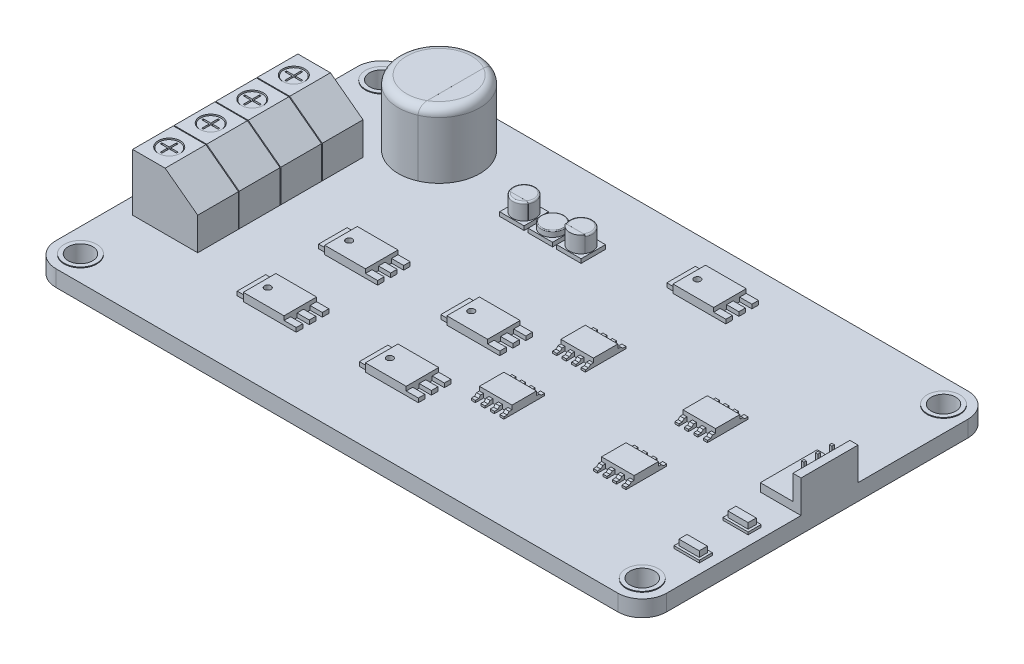
SolidWorks part; units mm, degrees
ref_plane "Front Plane" through (0, 0, 0) normal (0, 0, 1) x (1, 0, 0)
ref_plane "Top Plane" through (0, 0, 0) normal (0, 1, 0) x (1, 0, 0)
ref_plane "Right Plane" through (0, 0, 0) normal (1, 0, 0) x (0, 0, -1)
sketch "Sketch1" plane through (0, 0, 0) normal (0, 1, 0) x (1, 0, 0)
  line L1 (34.5, -21.5) -> (-34.5, -21.5)
  line L2 (37.5, -18.5) -> (37.5, 18.5)
  line L3 (34.5, 21.5) -> (-34.5, 21.5)
  line L4 (-37.5, -18.5) -> (-37.5, 18.5)
  line L5 (37.5, -21.5) -> (-37.5, 21.5) construction
  line L6 (37.5, 21.5) -> (-37.5, -21.5) construction
  circle A0 centre (-34.5, 18.5) radius 1.5
  circle A1 centre (34.5, 18.5) radius 1.5
  circle A2 centre (34.5, -18.5) radius 1.5
  circle A3 centre (-34.5, -18.5) radius 1.5
  arc A4 (-34.5, -21.5) -> (-37.5, -18.5) centre (-34.5, -18.5) cw
  arc A5 (34.5, -21.5) -> (37.5, -18.5) centre (34.5, -18.5) ccw
  arc A6 (-34.5, 21.5) -> (-37.5, 18.5) centre (-34.5, 18.5) ccw
  arc A7 (37.5, 18.5) -> (34.5, 21.5) centre (34.5, 18.5) ccw
  point P0 (0, 0)
  dimension "D3" = 3
  dimension "D8" = 3
  dimension "D1" = 75
  dimension "D2" = 43
  dimension "D4" = 37
  dimension "D5" = 18.5
  dimension "D6" = 69
  dimension "D7" = 34.5
extrude "Boss-Extrude1" add sketch "Sketch1" along normal blind 2
ref_plane "Plane1" through (0, 0, 1) normal (0, 0, 1) x (1, 0, 0)
sketch "Sketch8" plane through (0, 0, 1) normal (0, 0, 1) x (1, 0, 0)
  line L0 (-35.5, 2) -> (-35.5, 9)
  line L1 (-34.5, 2) -> (34.5, 2) construction
  line L2 (-35.5, 9) -> (-31.5, 9)
  line L3 (-31.5, 9) -> (-27.5, 6)
  line L4 (-27.5, 6) -> (-27.5, 2)
  line L5 (-27.5, 2) -> (-35.5, 2)
  line L6 (-37.5, 2) -> (-37.5, 0) construction
  dimension "D1" = 2
  dimension "D2" = 7
  dimension "D3" = 8
  dimension "D4" = 4
  dimension "D5" = 4
extrude "Boss-Extrude3" add sketch "Sketch8" along normal blind 5
sketch "Sketch9" plane through (0, 9, 0) normal (0, 1, 0) x (1, 0, 0)
  line L0 (-31.5, -1) -> (-35.5, -1) construction
  line L1 (-35.5, -6) -> (-35.5, -1) construction
  line L2 (-33.5, -3.5) -> (-33.5, -2.5)
  line L3 (-33.4, -4.5) -> (-33.4, -3.5)
  line L4 (-33.5, -4.5) -> (-33.5, -3.5)
  line L5 (-32.5, -3.5) -> (-34.5, -3.5)
  line L6 (-33.4, -3.5) -> (-33.4, -2.5)
  line L7 (-32.5, -3.4) -> (-34.5, -3.4)
  line L8 (-33.6, -4.5) -> (-33.6, -3.5)
  line L9 (-33.6, -3.5) -> (-33.6, -2.5)
  line L10 (-32.5, -3.6) -> (-34.5, -3.6)
  line L11 (-33.6, -2.5) -> (-33.4, -2.5)
  line L12 (-32.5, -3.4) -> (-32.5, -3.6)
  line L13 (-33.4, -4.5) -> (-33.6, -4.5)
  line L14 (-34.5, -3.6) -> (-34.5, -3.4)
  circle A0 centre (-33.5, -3.5) radius 1.25
  circle A1 centre (-33.5, -3.5) radius 1.35
  dimension "D1" = 2.5
  dimension "D2" = 2.5
  dimension "D3" = 2
  dimension "D5" = 1
  dimension "D6" = 1
  dimension "D7" = 1
  dimension "D8" = 1
  dimension "D4" = 0.1
  dimension "D9" = 0.1
  dimension "D10" = 0.1
extrude "Cut-Extrude2" cut sketch "Sketch9" against normal blind 2.5 contours A1 A0 region at (-34.8118, 9, 3.5)
extrude "Cut-Extrude4" cut sketch "Sketch9<4>" against normal blind 0.1 contours A0
sketch "Sketch9<4>" plane through (0, 9, 0) normal (0, 1, 0) x (1, 0, 0) same geometry as "Sketch9"
extrude "Cut-Extrude3" cut sketch "Sketch9<3>" against normal blind 0.5 contours L11 L2 L7 L6 | L11 L9 L7 L2 | L13 L3 L10 L4 | L13 L4 L10 L8 | L7 L14 L10 L12 region at (-33.55, 9, 2.95) region at (-33.45, 9, 2.95) region at (-33.45, 9, 4.05) region at (-33.55, 9, 4.05)
sketch "Sketch9<3>" plane through (0, 9, 0) normal (0, 1, 0) x (1, 0, 0) same geometry as "Sketch9"
pattern_linear "LPattern1" count 2 spacing 5.1 along (0, 0, 1) count 3 spacing 5.1 along (0, 0, -1) of "Boss-Extrude3", "Cut-Extrude2", "Cut-Extrude4", "Cut-Extrude3" pattern seed only yes
sketch "Sketch10" plane through (0, 2, 0) normal (0, 1, 0) x (1, 0, 0)
  circle A0 centre (-34.5, 18.5) radius 1.5 construction
  circle A11 centre (-34.5, 18.5) radius 2
  circle A12 centre (-34.5, 18.5) radius 2
  circle A14 centre (34.5, 18.5) radius 2
  circle A15 centre (34.5, 18.5) radius 2
  circle A17 centre (34.5, -18.5) radius 2
  circle A18 centre (34.5, -18.5) radius 2
  circle A19 centre (-34.5, -18.5) radius 1.5
  circle A20 centre (-34.5, -18.5) radius 2
  circle A21 centre (-34.5, -18.5) radius 2
  circle A22 centre (-34.5, 18.5) radius 1.5
  circle A23 centre (34.5, 18.5) radius 1.5
  circle A24 centre (34.5, -18.5) radius 1.5
  dimension "D1" = 0.5
  dimension "D2" = 0.5
  dimension "D3" = 0.5
  dimension "D4" = 0.5
extrude "Boss-Extrude4" add sketch "Sketch10" along normal blind 0.1
sketch "Sketch11" plane through (0, 2, 0) normal (0, 1, 0) x (1, 0, 0)
  circle A0 centre (-23.5927, 14.6414) radius 5
  point P2 (0, 0)
  point P3 (-17.5, 14.1677)
  point P4 (0, 0)
  point P6 (-23.5927, 14.6414)
  point P8 (0, 0)
  point P9 (0, 0)
  dimension "D2" = 10
extrude "Boss-Extrude5" add sketch "Sketch11" along normal blind 8
fillet "Fillet1" radius 1 1 edges at (-23.5927, 10, -9.6414)
sketch "Sketch12" plane through (0, 2, 0) normal (0, 1, 0) x (1, 0, 0)
  line L0 (-37.5, 18.5) -> (-37.5, -18.5) construction
  line L1 (-19.5, -3.5) -> (-14.5, -3.5)
  line L2 (-19.5, -3.5) -> (-19.5, 0.5)
  line L3 (-19.5, 0.5) -> (-14.5, 0.5)
  line L4 (-14.5, -3.5) -> (-14.5, 0.5)
  line L5 (-34.5, -21.5) -> (34.5, -21.5) construction
  line L6 (-14.5, -3.5) -> (-13, -3.5)
  line L7 (-13, -3.5) -> (-13, -2.7)
  line L8 (-13, -2.7) -> (-14.5, -2.7)
  line L9 (-14.5, -1.901) -> (-13, -1.901)
  line L10 (-13, -1.901) -> (-13, -1.101)
  line L11 (-13, -1.101) -> (-14.5, -1.101)
  line L12 (-14.5, 0.5) -> (-13, 0.5)
  line L13 (-13, 0.5) -> (-13, -0.301)
  line L14 (-13, -0.301) -> (-14.5, -0.301)
  circle A0 centre (-18.5, -1.5) radius 0.4
  point P21 (-19.5, -1.5)
  dimension "D10" = 0.8
  dimension "D1" = 4
  dimension "D2" = 5
  dimension "D3" = 18
  dimension "D4" = 18
  dimension "D5" = 0.8
  dimension "D6" = 0.8
  dimension "D7" = 0.801
  dimension "D8" = 0.8
  dimension "D9" = 1.5
  dimension "D11" = 1
extrude "Boss-Extrude6" add sketch "Sketch12" along normal blind 1 contours L1 L4 L3 L2 region at (-16.9613, 2, 1.5)
extrude "Boss-Extrude7" add sketch "Sketch12<3>" along normal blind 0.5 contours L14 L13 L12 L4 | L10 L11 L4 L9 | L7 L8 L4 L6 region at (-13.75, 2, 3.1) region at (-13.75, 2, -0.0995) region at (-13.75, 2, 1.501)
sketch "Sketch12<3>" plane through (0, 2, 0) normal (0, 1, 0) x (1, 0, 0) same geometry as "Sketch12"
sketch "Sketch13" plane through (-19.5, 0, 0) normal (-1, 0, 0) x (0, 0, 1)
  line L0 (3.5, 2) -> (-0.5, 2) construction
  line L1 (-0.25, 2) -> (3.25, 2)
  line L2 (-0.25, 2) -> (-0.25, 2.5025)
  line L3 (-0.25, 2.5025) -> (3.25, 2.5025)
  line L4 (3.25, 2) -> (3.25, 2.5025)
  line L5 (3.5, 3) -> (-0.5, 3) construction
  point P6 (1.5, 2.5025)
  point P9 (1.5, 3)
  dimension "D1" = 0.5025
  dimension "D2" = 3.5
extrude "Boss-Extrude8" add sketch "Sketch13" along normal blind 1
pattern_linear "LPattern3" count 2 spacing 10 along (0, 0, 1) count 2 spacing 15 along (1, 0, 0) of "Boss-Extrude6", "Boss-Extrude7", "Boss-Extrude8"
sketch "Sketch14" plane through (0, 10, 0) normal (0, 1, 0) x (1, 0, 0)
  line L0 (-21.5927, 19.2239) -> (-21.5927, 10.0588)
  circle A0 centre (-23.5927, 14.6414) radius 5
  circle M4 centre (-23.5927, 14.6414) radius 4
  dimension "D1" = 10
  dimension "D2" = 3
extrude "Cut-Extrude5" cut sketch "Sketch14" against normal up to surface (8 mm away) contours L0 M4 | L0 A0 M4 region at (-19.4901, 10, -17.3272) region at (-20.7726, 10, -14.6414) up to face at (-15.9375, 2, 11.5004)
sketch "Sketch15" plane through (0, 2, 0) normal (0, 1, 0) x (1, 0, 0)
  line L0 (-21.5917, 19.2235) -> (-21.5917, 10.0588)
  line L3 (-21.5927, 19.2239) -> (-21.5927, 10.0588) construction
  circle A0 centre (-23.5927, 14.6414) radius 5
  point P3 (-21.5917, 19.2235)
  point P4 (-21.5927, 10.0588)
  dimension "D1" = 10
  dimension "D3" = 0.001
extrude "Boss-Extrude9" add sketch "Sketch15" along normal up to surface (8 mm away) contours L0 A0 region at (-20.3547, 2, -14.6414) up to face at (-24.5927, 10, -14.6414)
fillet "Fillet2" radius 1 1 edges at (-18.5927, 10, -14.6414)
sketch "Sketch16" plane through (0, 2, 0) normal (0, 1, 0) x (1, 0, 0)
  line L0 (6, 13.767) -> (11, 13.767)
  line L1 (6, 13.767) -> (6, 17.767)
  line L2 (6, 17.767) -> (11, 17.767)
  line L3 (11, 13.767) -> (11, 17.767)
  line L4 (11, 17.767) -> (12.5, 17.767)
  line L5 (12.5, 17.767) -> (12.5, 16.967)
  line L6 (12.5, 16.967) -> (11, 16.967)
  line L7 (11, 16.167) -> (12.5, 16.167)
  line L8 (12.5, 16.167) -> (12.5, 15.367)
  line L9 (12.5, 15.367) -> (11, 15.367)
  line L10 (11, 13.767) -> (12.5, 13.767)
  line L11 (12.5, 13.767) -> (12.5, 14.567)
  line L12 (12.5, 14.567) -> (11, 14.567)
  circle A0 centre (7, 15.767) radius 0.4
  point P5 (6, 15.767)
  point P18 (0, 0)
  point P19 (0, 0)
  point P20 (7, 15.767)
  dimension "D9" = 0.8
  dimension "D1" = 4
  dimension "D2" = 5
  dimension "D3" = 0.8
  dimension "D4" = 1.5
  dimension "D5" = 0.8
  dimension "D6" = 0.8
  dimension "D7" = 0.8
  dimension "D8" = 6
  dimension "D10" = 1
extrude "Boss-Extrude10" add sketch "Sketch16" along normal blind 1 contours L0 L3 L2 L1 region at (8.5387, 2, -15.767)
extrude "Boss-Extrude11" add sketch "Sketch16<3>" along normal blind 0.5 contours L6 L5 L4 L3 | L9 L8 L7 L3 | L11 L12 L3 L10 region at (11.75, 2, -14.167) region at (11.75, 2, -17.367) region at (11.75, 2, -15.767)
sketch "Sketch16<3>" plane through (0, 2, 0) normal (0, 1, 0) x (1, 0, 0) same geometry as "Sketch16"
sketch "Sketch17" plane through (6, 0, 0) normal (-1, 0, 0) x (0, 0, 1)
  line L0 (-13.767, 2) -> (-17.767, 2) construction
  line L1 (-17.517, 2) -> (-14.017, 2)
  line L2 (-17.517, 2) -> (-17.517, 2.5)
  line L3 (-17.517, 2.5) -> (-14.017, 2.5)
  line L4 (-14.017, 2) -> (-14.017, 2.5)
  line L5 (-13.767, 3) -> (-17.767, 3) construction
  point P6 (-15.767, 2.5)
  point P9 (-15.767, 3)
  dimension "D1" = 0.5
  dimension "D2" = 3.5
extrude "Boss-Extrude12" add sketch "Sketch17" along normal blind 1
sketch "Sketch18" plane through (0, 2, 0) normal (0, 1, 0) x (1, 0, 0)
  line L0 (5, 4) -> (5, 5)
  line L1 (5, 4) -> (9, 4)
  line L2 (5, 4) -> (5, 1)
  line L3 (5, 1) -> (9, 1)
  line L4 (9, 4) -> (9, 1)
  line L5 (5, 5) -> (5.5, 5)
  line L6 (5.5, 5) -> (5.5, 4)
  line L7 (6.1633, 4) -> (6.1633, 5)
  line L8 (6.1633, 5) -> (6.6633, 5)
  line L9 (6.6633, 5) -> (6.6633, 4)
  line L10 (7.3333, 4) -> (7.3333, 5)
  line L11 (7.3333, 5) -> (7.8333, 5)
  line L12 (7.8333, 5) -> (7.8333, 4)
  line L13 (8.5, 4) -> (8.5, 5)
  line L14 (8.5, 5) -> (9, 5)
  line L15 (9, 5) -> (9, 4)
  line L16 (9, 1) -> (9, 0)
  line L17 (9, 0) -> (8.5, 0)
  line L18 (8.5, 0) -> (8.5, 1)
  line L19 (7.8333, 1) -> (7.8333, 0)
  line L20 (7.8333, 0) -> (7.3333, 0)
  line L21 (7.3333, 0) -> (7.3333, 1)
  line L22 (6.6633, 1) -> (6.6633, 0)
  line L23 (6.6633, 0) -> (6.1633, 0)
  line L24 (6.1633, 0) -> (6.1633, 1)
  line L25 (5, 1) -> (5, 0)
  line L26 (5, 0) -> (5.5, 0)
  line L27 (5.5, 0) -> (5.5, 1)
  dimension "D1" = 3
  dimension "D2" = 4
  dimension "D3" = 0.5
  dimension "D4" = 0.5
  dimension "D5" = 0.6667
  dimension "D6" = 0.67
  dimension "D7" = 0.5
  dimension "D8" = 0.5
  dimension "D9" = 1
  dimension "D10" = 5
  dimension "D11" = 4
extrude "Boss-Extrude13" add sketch "Sketch18" along normal blind 1 contours L4 L1 L2 L3 region at (7, 2, -2.5)
extrude "Boss-Extrude14" add sketch "Sketch18<3>" along normal blind 0.5 contours L18 L17 L16 L3 | L21 L20 L19 L3 | L24 L23 L22 L3 | L26 L27 L3 L25 | L15 L14 L13 L1 | L12 L11 L10 L1 | L9 L8 L7 L1 | L6 L5 L0 L1 region at (5.25, 2, -4.5) region at (5.25, 2, -0.5) region at (6.4133, 2, -4.5) region at (6.4133, 2, -0.5) region at (7.5833, 2, -4.5) region at (7.5833, 2, -0.5) region at (8.75, 2, -4.5) region at (8.75, 2, -0.5)
sketch "Sketch18<3>" plane through (0, 2, 0) normal (0, 1, 0) x (1, 0, 0) same geometry as "Sketch18"
sketch "Sketch19" plane through (9, 0, 0) normal (1, 0, 0) x (0, 0, -1)
  line L0 (-18.5, 2) -> (18.5, 2) construction
  line L1 (0, 2.5) -> (1, 2.5)
  line L2 (0, 2.5) -> (0, 2)
  line L3 (0, 2) -> (1, 2)
  line L4 (1, 2.5) -> (1, 2)
  line L5 (1, 2.5) -> (0.6524, 2.5)
  line L6 (0.6524, 2.5) -> (0.4024, 2.25)
  line L7 (0.4024, 2.25) -> (0, 2.25)
  line L8 (2.5, 3) -> (2.5, 2) construction
  line L9 (4, 3) -> (1, 3) construction
  line L10 (5, 2) -> (0, 2) construction
  line L11 (4.5976, 2.25) -> (5, 2.25)
  line L12 (4.3476, 2.5) -> (4.5976, 2.25)
  line L13 (5, 2) -> (4, 2)
  line L14 (4, 2.5) -> (4, 2)
  line L15 (5, 2.5) -> (4, 2.5)
  line L16 (5, 2.5) -> (5, 2)
  line M9 (5, 2) -> (5, 2.5)
  line M10 (5, 2.5) -> (4, 2.5)
  line M15 (0, 2.5) -> (0, 2)
  dimension "D1" = 0.25
  dimension "D2" = 0.3476
extrude "Cut-Extrude6" cut sketch "Sketch19" against normal up to surface (4 mm away) contours L7 L6 L1 M15 | L12 L11 M10 M9 region at (9, 2.3849, -0.2686) region at (9, 2.3849, -4.7314) up to face at (5, 2.5, -2.5)
pattern_linear "LPattern4" count 2 spacing 10 along (0, 0, 1) count 2 spacing 15 along (1, 0, 0) of "Boss-Extrude13", "Cut-Extrude6", "Boss-Extrude14"
sketch "Sketch20" plane through (0, 2, 0) normal (0, 1, 0) x (1, 0, 0)
  line L1 (-12.825, 14.3088) -> (-9.825, 14.3088)
  line L2 (-12.825, 14.3088) -> (-12.825, 11.3088)
  line L3 (-12.825, 11.3088) -> (-9.825, 11.3088)
  line L4 (-9.825, 14.3088) -> (-9.825, 11.3088)
  point P4 (-12.825, 11.3088)
  dimension "D1" = 3
  dimension "D2" = 3
extrude "Boss-Extrude15" add sketch "Sketch20" along normal blind 0.5
pattern_linear "LPattern5" count 3 spacing 3.5 along (1, 0, 0) of "Boss-Extrude15"
sketch "Sketch21" plane through (0, 2.5, 0) normal (0, 1, 0) x (1, 0, 0)
  line L0 (-9.825, 14.3088) -> (-12.825, 14.3088) construction
  line L1 (-12.825, 14.3088) -> (-12.825, 11.3088) construction
  circle A0 centre (-11.325, 12.8088) radius 1.4
  point P6 (-11.325, 14.3088)
  point P10 (-12.825, 12.8088)
  dimension "D1" = 2.8
extrude "Boss-Extrude16" add sketch "Sketch21" along normal blind 2
sketch "Sketch22" plane through (0, 4.5, 0) normal (0, 1, 0) x (1, 0, 0)
  line L0 (-12.5375, 12.1088) -> (-10.1126, 12.1088)
  circle A0 centre (-11.325, 12.8088) radius 1.4
  circle M3 centre (-11.325, 12.8088) radius 1.4
  dimension "D1" = 2.8
  dimension "D2" = 0.7
extrude "Cut-Extrude7" cut sketch "Sketch22" against normal up to surface (2 mm away) contours L0 M3 region at (-11.325, 4.5, -11.8217) up to face at (-11.325, 2.5, -11.4088)
sketch "Sketch23" plane through (0, 4.5, 0) normal (0, 1, 0) x (1, 0, 0)
  line L0 (-12.5369, 12.1078) -> (-10.1132, 12.1078)
  line L1 (-12.5375, 12.1088) -> (-10.1126, 12.1088) construction
  circle A0 centre (-11.325, 12.8088) radius 1.4
  dimension "D1" = 2.8
  dimension "D2" = 0.001
extrude "Boss-Extrude17" add sketch "Sketch23" against normal up to surface (2 mm away) contours L0 A0 region at (-11.325, 4.5, -11.8212) up to face at (-11.325, 2.5, -13.1588)
fillet "Fillet3" radius 0.2 1 edges at (-11.325, 4.5, -11.4088)
fillet "Fillet4" radius 0.2 1 edges at (-11.325, 4.5, -14.2088)
pattern_linear "LPattern6" count 2 spacing 7 along (1, 0, 0) of "Boss-Extrude16", "Boss-Extrude17", "Fillet4", "Cut-Extrude7"
sketch "Sketch24" plane through (0, 2.5, 0) normal (0, 1, 0) x (1, 0, 0)
  line L0 (-6.325, 14.3088) -> (-9.325, 14.3088) construction
  line L1 (-9.325, 14.3088) -> (-9.325, 11.3088) construction
  circle A0 centre (-7.825, 12.8088) radius 1.4
  point P5 (-7.825, 14.3088)
  point P9 (-9.325, 12.8088)
  dimension "D1" = 2.8
extrude "Boss-Extrude18" add sketch "Sketch24" along normal blind 0.7
fillet "Fillet5" radius 0.1 1 edges at (-7.825, 3.2, -11.4088)
sketch "Sketch25" plane through (0, 2, 0) normal (0, 1, 0) x (1, 0, 0)
  line L0 (37.5, -18.5) -> (37.5, 18.5) construction
  line L1 (32.5, 5) -> (37.5, 5)
  line L2 (32.5, 5) -> (32.5, -2)
  line L3 (32.5, -2) -> (37.5, -2)
  line L4 (37.5, 5) -> (37.5, -2)
  line L5 (34.5, 21.5) -> (-34.5, 21.5) construction
  dimension "D1" = 7
  dimension "D2" = 5
  dimension "D3" = 16.5
extrude "Boss-Extrude19" add sketch "Sketch25" along normal blind 1
sketch "Sketch26" plane through (0, 3, 0) normal (0, 1, 0) x (1, 0, 0)
  line L0 (32.5, -2) -> (37.5, -2) construction
  line L1 (37.5, 5) -> (36.5, 5)
  line L2 (37.5, 5) -> (37.5, -2)
  line L3 (37.5, -2) -> (36.5, -2)
  line L4 (36.5, 5) -> (36.5, -2)
  dimension "D1" = 1
extrude "Boss-Extrude20" add sketch "Sketch26" along normal blind 3
sketch "Sketch27" plane through (0, 3, 0) normal (0, 1, 0) x (1, 0, 0)
  line L0 (36.5, 5) -> (36.5, -2) construction
  line L1 (35.7, 3.58) -> (36, 3.58)
  line L2 (35.7, 3.58) -> (35.7, 3.28)
  line L3 (35.7, 3.28) -> (36, 3.28)
  line L4 (36, 3.58) -> (36, 3.28)
  line L5 (36.5, 5) -> (32.5, 5) construction
  line L6 (35.7, 1.8633) -> (35.7, 1.5633)
  line L7 (35.7, 1.8633) -> (36, 1.8633)
  line L8 (36, 1.8633) -> (36, 1.5633)
  line L9 (35.7, 1.5633) -> (36, 1.5633)
  line L10 (35.7, 0.1467) -> (35.7, -0.1533)
  line L11 (35.7, 0.1467) -> (36, 0.1467)
  line L12 (36, 0.1467) -> (36, -0.1533)
  line L13 (35.7, -0.1533) -> (36, -0.1533)
  dimension "D1" = 0.3
  dimension "D2" = 0.5
  dimension "D3" = 1.42
  dimension "D5" = 1.4167
  dimension "D4" = 3
extrude "Boss-Extrude21" add sketch "Sketch27" along normal blind 3
sketch "Sketch28" plane through (0, 2, 0) normal (0, 1, 0) x (1, 0, 0)
  line L0 (32.5, -2) -> (36.5, -2) construction
  line L1 (33.5, -6) -> (36, -6)
  line L2 (33.5, -6) -> (33.5, -7)
  line L3 (33.5, -7) -> (36, -7)
  line L4 (36, -6) -> (36, -7)
  line L5 (37.5, -18.5) -> (37.5, -2) construction
  dimension "D1" = 4
  dimension "D2" = 1
  dimension "D3" = 2.5
  dimension "D4" = 1.5
extrude "Boss-Extrude22" add sketch "Sketch28" along normal blind 1
sketch "Sketch29" plane through (0, 2, 0) normal (0, 1, 0) x (1, 0, 0)
  line L8 (33.2, -5.7) -> (33.2, -7.3)
  line L9 (33.2, -7.3) -> (36.3, -7.3)
  line L10 (36.3, -7.3) -> (36.3, -5.7)
  line L11 (36.3, -5.7) -> (33.2, -5.7)
  line L12 (33.2, -5.7) -> (33.2, -7.3)
  line L13 (33.2, -7.3) -> (36.3, -7.3)
  line L14 (36.3, -7.3) -> (36.3, -5.7)
  line L15 (36.3, -5.7) -> (33.2, -5.7)
  dimension "D1" = 0.3
extrude "Boss-Extrude23" add sketch "Sketch29" along normal blind 0.3
pattern_linear "LPattern7" count 2 spacing 6 along (0, 0, 1) of "Boss-Extrude23", "Boss-Extrude22"
